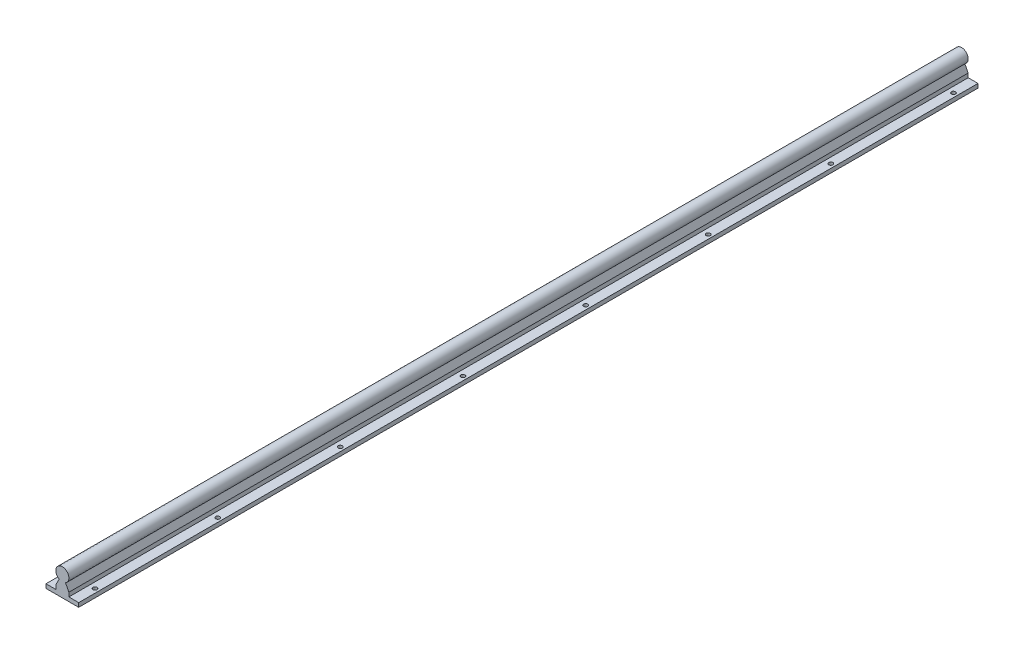
SolidWorks part; units mm, degrees
ref_plane "Front Plane" through (0, 0, 0) normal (0, 0, 1) x (1, 0, 0)
ref_plane "Top Plane" through (0, 0, 0) normal (0, 1, 0) x (1, 0, 0)
ref_plane "Right Plane" through (0, 0, 0) normal (1, 0, 0) x (0, 0, -1)
sketch "Sketch2" plane through (0, 0, 0) normal (0, 0, 1) x (1, 0, 0)
  line L0 (-20, 0) -> (20, 0)
  line L1 (20, 0) -> (20, 5)
  line L2 (-20, 0) -> (-20, 5)
  line L3 (-20, 5) -> (-8, 5)
  line L4 (20, 5) -> (8, 5)
  line L5 (-8, 5) -> (-8, 10)
  line L6 (8, 5) -> (8, 10)
  line L8 (-8, 10) -> (-3.873, 18)
  line L9 (8, 10) -> (3.873, 18)
  circle A0 centre (0, 25) radius 8
  dimension "D1" = 16
  dimension "D2" = 40
  dimension "D3" = 5
  dimension "D4" = 5
  dimension "D5" = 25
  dimension "D6" = 12
  dimension "D7" = 12
  dimension "D8" = 5
  dimension "D9" = 5
  dimension "D10" = 20
extrude "Boss-Extrude3" add sketch "Sketch2" along normal blind 1100 contours A0 L8 L5 L3 L2 L0 L1 L4 L6 L9 region at (0, 6.2033, 0)
extrude "Boss-Extrude4" add sketch "Sketch2<4>" along normal blind 1100 contours A0 region at (0, 25, 0)
sketch "Sketch2<4>" plane through (0, 0, 0) normal (0, 0, 1) x (1, 0, 0) same geometry as "Sketch2"
hole_wizard "Ø5.0mm Dowel Hole1" positions "Sketch4" profile "Sketch3" hole size "Ø5.0" standard "ISO" end condition through all
sketch "Sketch4" plane through (0, 5, 0) normal (0, 1, 0) x (1, 0, 0)
  line L0 (20, -1100) -> (8, -1100) construction
  line L1 (20, -1100) -> (20, 0) construction
  line L2 (-20, -1100) -> (-20, 0) construction
  line L3 (-20, -1100) -> (-8, -1100) construction
  point P0 (15, -1075)
  point P5 (-15, -1075)
  point P12 (-14, -1100)
  dimension "D1" = 25
  dimension "D2" = 5
  dimension "D3" = 5
  dimension "D4" = 25
sketch "Sketch3" plane through (15, 5, 1075) normal (1, 0, 0) x (0, 0, 1)
  line L0 (0, 0) -> (0, 5)
  line L1 (0, 5) -> (2.5, 5)
  line L2 (2.5, 5) -> (2.5, 0)
  line L5 (2.5, 0) -> (0, 0)
  line L11 (0, -6.35) -> (0, 107.95) construction
  dimension "Thru Hole Dia." = 5
  dimension "Thru Hole Depth" = 5
pattern_linear "LPattern1" count 8 spacing 150 along (0, 0, -1) of "Ø5.0mm Dowel Hole1"
